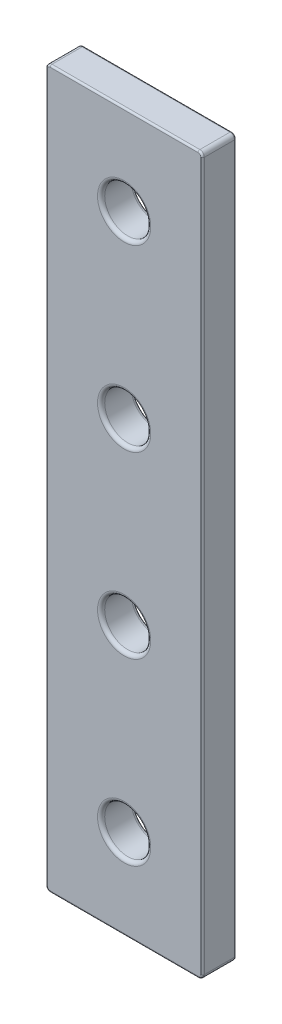
SolidWorks part; units mm, degrees
ref_plane "Front Plane" through (0, 0, 0) normal (0, 0, 1) x (1, 0, 0)
ref_plane "Top Plane" through (0, 0, 0) normal (0, 1, 0) x (1, 0, 0)
ref_plane "Right Plane" through (0, 0, 0) normal (1, 0, 0) x (0, 0, -1)
sketch "Sketch1" plane through (0, 0, 0) normal (0, 0, 1) x (1, 0, 0)
  line L0 (-11.1125, 50.8) -> (-11.1125, -50.8)
  line L1 (-11.1125, 50.8) -> (11.1125, 50.8)
  line L2 (-11.1125, -50.8) -> (11.1125, -50.8)
  line L3 (11.1125, 50.8) -> (11.1125, -50.8)
  line L4 (-11.1125, 0) -> (11.1125, 0) construction
  line L5 (0, 12.7) -> (0, 38.1) construction
  line L6 (-3.175, 38.1) -> (-1.905, 38.1) construction
  circle A0 centre (0, 38.1) radius 3.2639
  circle A2 centre (0, 38.1) radius 3.175 construction
  circle A3 centre (25.4, 38.1) radius 3.2639
  circle A4 centre (25.4, 12.7) radius 3.2639
  circle A5 centre (0, 12.7) radius 3.2639
  circle A6 centre (0, -12.7) radius 3.2639
  circle A7 centre (25.4, -12.7) radius 3.2639
  circle A8 centre (0, -38.1) radius 3.2639
  circle A9 centre (25.4, -38.1) radius 3.2639
  dimension "Thru Hole Diameter" = 6.5278
  dimension "Mounting Fastener Thread Size" = 6.35
  dimension "Width" = 22.225
  dimension "Length" = 101.6
  dimension "Mounting Hole Vert CtoC" = 25.4
  dimension "Mounting Fastener Thread Pitch" = 1.27
  dimension "D1" = 63.5
  dimension "D2" = 11.1125
  dimension "Mounting Hole Horiz CtoC" = 25.4
  dimension "Mounting Hole Vertical Offset" = 12.7
  dimension "Mounting Hole Horizontal Offset" = 11.1125
  dimension "D50" = 2
  dimension "Number of Vertical Holes" = 4
sketch "Sketch2" plane through (0, 0, 0) normal (1, 0, 0) x (0, 0, -1)
  line L0 (-2.3876, 38.1) -> (2.3876, 38.1) construction
  line L1 (2.3876, 38.1) -> (15.0749, 38.1) construction
  dimension "Thickness" = 4.7752
  dimension "Mounting Fastener Thread Length" = 17.4625
sketch "Sketch3" plane through (0, 0, 0) normal (0, 0, 1) x (1, 0, 0)
  line L0 (-11.1125, 50.8) -> (-11.1125, -50.8) construction
  line L1 (-11.1125, -50.8) -> (11.1125, -50.8) construction
  line L2 (11.1125, 50.8) -> (11.1125, -50.8) construction
  line L3 (-11.1125, 50.8) -> (11.1125, 50.8) construction
  line L4 (-11.1125, 50.8) -> (-11.1125, -50.8)
  line L5 (-11.1125, -50.8) -> (11.1125, -50.8)
  line L6 (11.1125, 50.8) -> (11.1125, -50.8)
  line L7 (-11.1125, 50.8) -> (11.1125, 50.8)
extrude "Boss-Extrude1" add sketch "Sketch3" along normal up to vertex (2.3876 mm away) from vertex up to point (0, 38.1, 2.3876) starting at point (0, 38.1, -2.3876)
fillet "Fillet1" radius 0.635 4 edges at (11.1125, -50.8, 0) (-11.1125, -50.8, 0) (-11.1125, 50.8, 0) (11.1125, 50.8, 0)
sketch "Sketch4" plane through (0, 0, 2.3876) normal (0, 0, 1) x (1, 0, 0)
  circle A0 centre (0, 38.1) radius 3.2639 construction
  circle A1 centre (0, 38.1) radius 3.2639
extrude "Cut-Extrude1" cut sketch "Sketch4" against normal through all
pattern_linear "LPattern1" count 4 spacing 25.4 along (0, -1, 0) count 2 spacing 25.4 along (1, 0, 0) of "Cut-Extrude1"
fillet "Fillet2" radius 0.254 16 edges at (10.9265, -50.614, -2.3876) (0, -50.8, -2.3876) (-10.9265, -50.614, -2.3876) (-11.1125, 0, -2.3876) (-10.9265, 50.614, -2.3876) (0, 50.8, -2.3876) (10.9265, 50.614, -2.3876) (10.9265, -50.614, 2.3876) (0, -50.8, 2.3876) (-10.9265, -50.614, 2.3876) (-11.1125, 0, 2.3876) (-10.9265, 50.614, 2.3876) (0, 50.8, 2.3876) (10.9265, 50.614, 2.3876) (11.1125, 0, -2.3876) (11.1125, 0, 2.3876)
fillet "Fillet3" radius 0.508 8 edges at (3.2639, 38.1, -2.3876) (3.2639, 12.7, -2.3876) (3.2639, 38.1, 2.3876) (3.2639, 12.7, 2.3876) (3.2639, -38.1, -2.3876) (3.2639, -12.7, -2.3876) (3.2639, -38.1, 2.3876) (3.2639, -12.7, 2.3876)
equation "\"D1@LPattern1\"=\"Number of Vertical Holes@Sketch1\""
equation "\"D4@LPattern1\"=\"D3@LPattern1\""
equation "\"D3@LPattern1\"=\"Mounting Hole Vert CtoC@Sketch1\""
equation "\"Mounting Hole Horiz CtoC@Sketch1\"=\"Mounting Hole Vert CtoC@Sketch1\""
